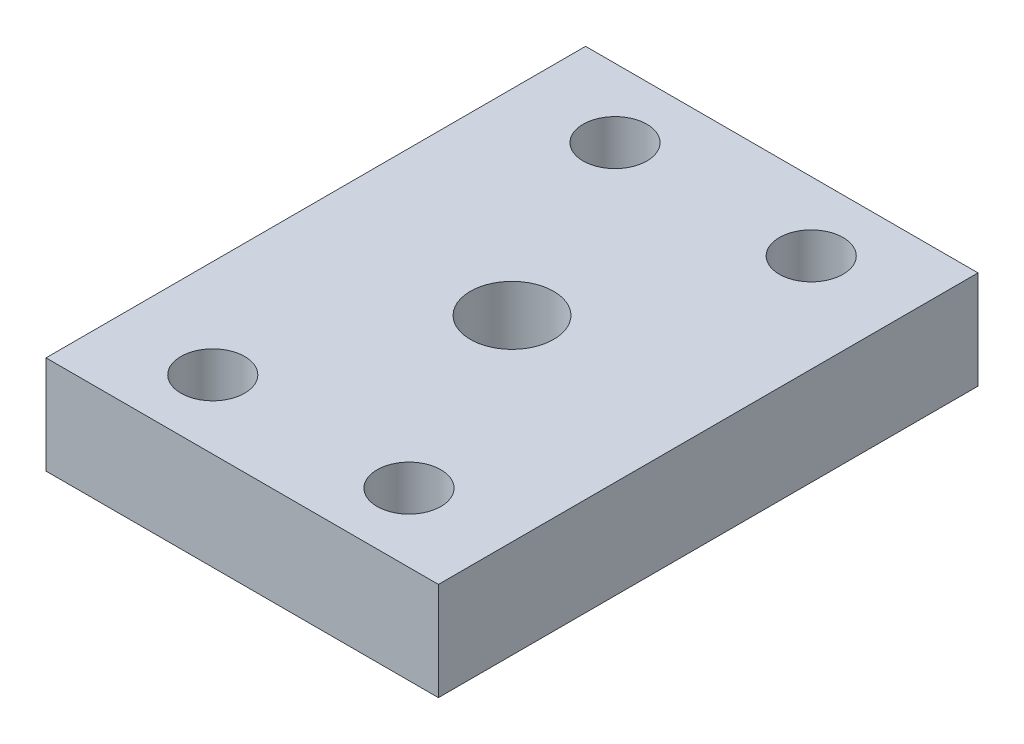
SolidWorks part; units mm, degrees
ref_plane "Front Plane" through (0, 0, 0) normal (0, 0, 1) x (1, 0, 0)
ref_plane "Top Plane" through (0, 0, 0) normal (0, 1, 0) x (1, 0, 0)
ref_plane "Right Plane" through (0, 0, 0) normal (1, 0, 0) x (0, 0, -1)
sketch "Sketch1" plane through (0, 0, 0) normal (0, 1, 0) x (1, 0, 0)
  line L0 (13.8021, -19.7414) -> (-19.1979, -19.7414) construction
  line L6 (-20.9185, -34.2414) -> (19.0815, -34.2414)
  line L7 (13.8021, 6.2586) -> (-15.6392, 6.2586) construction
  line L8 (13.8021, 6.2586) -> (13.8021, -19.7414) construction
  line L9 (13.8021, -19.7414) -> (-15.6392, -19.7414) construction
  line L10 (-15.6392, 6.2586) -> (-15.6392, -19.7414) construction
  line L11 (-15.6392, 6.2586) -> (13.8021, -19.7414) construction
  line L12 (-15.6392, -19.7414) -> (13.8021, 6.2586) construction
  line L13 (-20.9185, -34.2414) -> (-20.9185, 20.7586)
  line L14 (-20.9185, 20.7586) -> (19.0815, 20.7586)
  line L15 (19.0815, -34.2414) -> (19.0815, 20.7586)
  line L16 (-20.9185, -34.2414) -> (19.0815, 20.7586) construction
  line L17 (-20.9185, 20.7586) -> (19.0815, -34.2414) construction
  point P0 (0, 0)
  point P1 (-0.9185, -6.7414)
  dimension "D1" = 55
  dimension "D2" = 40
extrude "Boss-Extrude1" add sketch "Sketch1" along normal blind 10
sketch "Sketch2" plane through (0, 0, 0) normal (0, -1, 0) x (1, 0, 0)
  line L0 (-0.9185, -20.7586) -> (-0.9185, 34.2414) construction
  line L1 (19.0815, -20.7586) -> (-20.9185, -20.7586) construction
  line L2 (-20.9185, 34.2414) -> (19.0815, 34.2414) construction
  circle A0 centre (-0.9185, 6.7414) radius 4.25
  dimension "D1" = 8.5
extrude "Cut-Extrude1" cut sketch "Sketch2" against normal up to next
sketch "Sketch5" plane through (0, 10, 0) normal (0, 1, 0) x (1, 0, 0)
  line L0 (-20.9185, -27.2414) -> (19.0815, -27.2414) construction
  line L1 (-20.9185, 20.7586) -> (-20.9185, -34.2414) construction
  line L2 (19.0815, -34.2414) -> (19.0815, 20.7586) construction
  line L3 (-20.9185, 13.7586) -> (19.0815, 13.7586) construction
  line L4 (-20.9185, -34.2414) -> (19.0815, -34.2414) construction
  line L5 (19.0815, 20.7586) -> (-20.9185, 20.7586) construction
  circle A0 centre (-10.9185, -27.2414) radius 3.25
  circle A1 centre (9.0815, -27.2414) radius 3.25
  circle A2 centre (-10.9185, 13.7586) radius 3.25
  circle A3 centre (9.0815, 13.7586) radius 3.25
  dimension "D3" = 6.5
  dimension "D4" = 6.5
  dimension "D5" = 6.5
  dimension "D6" = 6.5
  dimension "D1" = 7
  dimension "D2" = 7
  dimension "D7" = 10
  dimension "D8" = 10
  dimension "D9" = 10
  dimension "D10" = 10
extrude "Cut-Extrude3" cut sketch "Sketch5" against normal up to next
